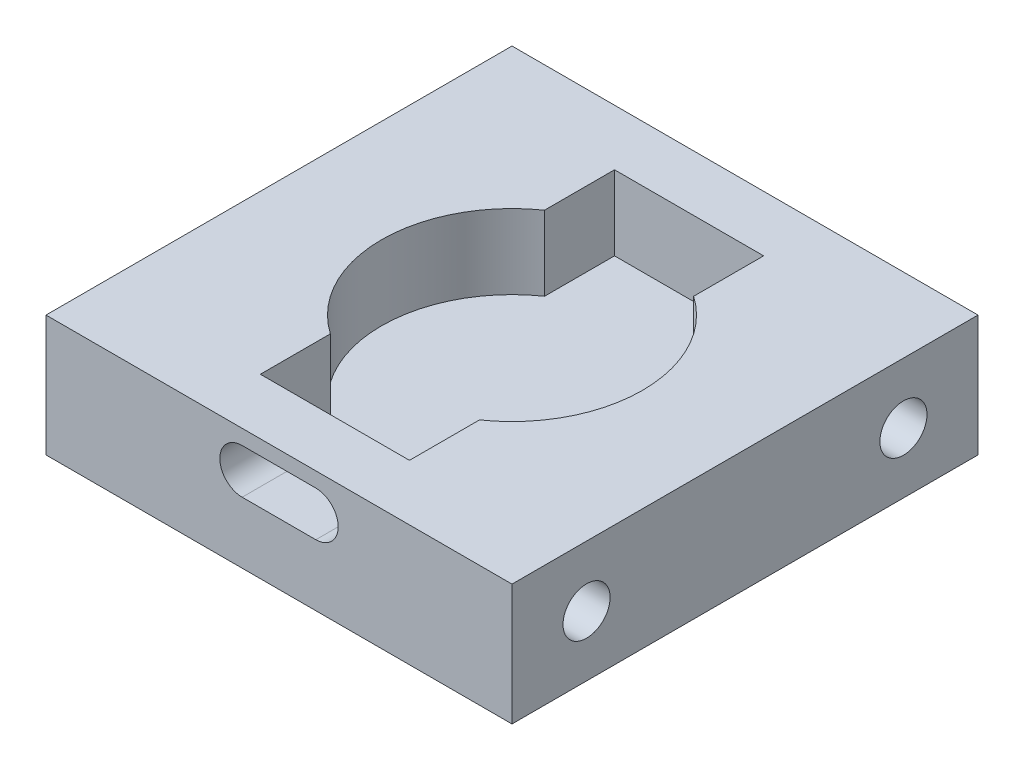
SolidWorks part; units mm, degrees
ref_plane "Front Plane" through (0, 0, 0) normal (0, 0, 1) x (1, 0, 0)
ref_plane "Top Plane" through (0, 0, 0) normal (0, 1, 0) x (1, 0, 0)
ref_plane "Right Plane" through (0, 0, 0) normal (1, 0, 0) x (0, 0, -1)
sketch "Sketch1" plane through (0, 0, 0) normal (0, 1, 0) x (1, 0, 0)
  line L1 (25, -25) -> (-25, -25)
  line L2 (25, -25) -> (25, 25)
  line L3 (25, 25) -> (-25, 25)
  line L4 (-25, -25) -> (-25, 25)
  line L5 (25, -25) -> (-25, 25) construction
  line L6 (25, 25) -> (-25, -25) construction
  line L7 (8, 19) -> (-8, 19)
  line L8 (8, 19) -> (8, -19)
  line L9 (8, -19) -> (-8, -19)
  line L10 (-8, 19) -> (-8, -19)
  line L11 (8, 19) -> (-8, -19) construction
  line L12 (8, -19) -> (-8, 19) construction
  circle A0 centre (0, 0) radius 14
  point P0 (0, 0)
  dimension "D3" = 28
  dimension "D1" = 50
  dimension "D2" = 50
  dimension "D4" = 16
  dimension "D5" = 38
extrude "Boss-Extrude1" add sketch "Sketch1" along normal blind 13 contours L4 L1 L2 L3 A0 L8 L9 L10 L7 region at (0, 0, 24.2929)
extrude "Boss-Extrude2" add sketch "Sketch1<3>" along normal blind 5 contours A0 L10 L9 L8 | L8 A0 L10 | L10 A0 | A0 L8 L7 L10 | L8 A0 region at (0, 0, -16.051) region at (10.4504, 0, 0) region at (0, 0, 0) region at (-10.4504, 0, 0) region at (0, 0, 16.051)
sketch "Sketch1<3>" plane through (0, 0, 0) normal (0, 1, 0) x (1, 0, 0) same geometry as "Sketch1"
hole_wizard "#8 (0.199) Diameter Hole1" positions "Sketch4" profile "Sketch5" hole size "#8" standard "ANSI Inch" end condition up to next
sketch "Sketch4" plane through (25, 0, 0) normal (1, 0, 0) x (0, 0, -1)
  line L0 (-25, 13) -> (25, 13) construction
  line L2 (-25, 13) -> (-25, 0) construction
  line L3 (25, 13) -> (25, 0) construction
  point P0 (-17, 6.5)
  point P2 (17, 6.5)
  point P11 (-25, 6.5)
  dimension "D1" = 6.5
  dimension "D2" = 6.5
  dimension "D3" = 8
  dimension "D4" = 8
sketch "Sketch5" plane through (25, 6.5, 17) normal (0, 1, 0) x (0, 0, -1)
  line L0 (0, 0) -> (0, 17)
  line L1 (0, 17) -> (2.5273, 17)
  line L2 (2.5273, 17) -> (2.5273, 0)
  line L5 (2.5273, 0) -> (0, 0)
  line L11 (0, -6.35) -> (0, 107.95) construction
  dimension "Thru Hole Dia." = 5.0546
  dimension "Thru Hole Depth" = 17
hole_wizard "#12 (0.189) Diameter Slot1" positions "Sketch6" profile "Sketch7" size "#12" standard "ANSI Inch" slot yes end condition up to next
sketch "Sketch6" plane through (0, 0, 25) normal (0, 0, 1) x (1, 0, 0)
  line L0 (-6.35, 9) -> (6.35, 9) construction
  line L1 (25, 0) -> (-25, 0) construction
  line L2 (-25, 13) -> (-25, 0) construction
  point P0 (0, 9)
  dimension "D1" = 12.7
  dimension "D2" = 9
  dimension "D3" = 25
sketch "Sketch7" plane through (0, 9, 25) normal (1, 0, 0) x (0, -1, 0)
  line L0 (0, 0) -> (0, 6)
  line L1 (0, 6) -> (2.4003, 6)
  line L2 (2.4003, 6) -> (2.4003, 0)
  line L5 (2.4003, 0) -> (0, 0)
  line L11 (0, -6.35) -> (0, 107.95) construction
  dimension "Thru Hole Dia." = 4.8006
  dimension "Thru Hole Depth" = 6
